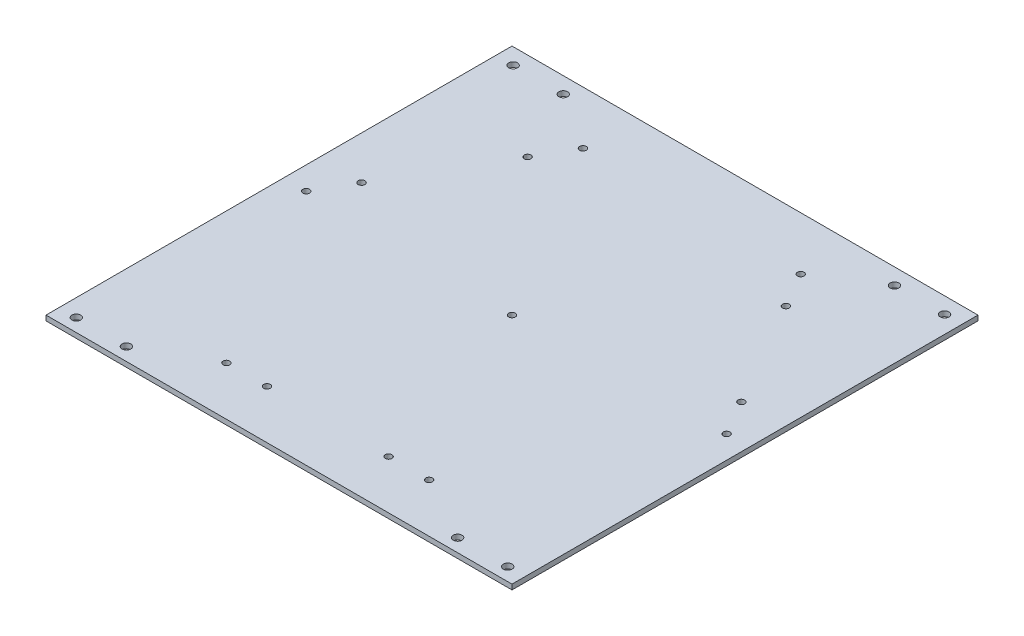
SolidWorks part; units mm, degrees
material "CA"
ref_plane "Front Plane" through (0, 0, 0) normal (0, 0, 1) x (1, 0, 0)
ref_plane "Top Plane" through (0, 0, 0) normal (0, 1, 0) x (1, 0, 0)
ref_plane "Right Plane" through (0, 0, 0) normal (1, 0, 0) x (0, 0, -1)
sketch "Sketch1" plane through (0, 0, 0) normal (0, 1, 0) x (1, 0, 0)
  line L1 (146.05, 146.05) -> (-146.05, 146.05)
  line L2 (-146.05, 146.05) -> (-146.05, -146.05)
  line L3 (-146.05, -146.05) -> (146.05, -146.05)
  line L4 (146.05, -146.05) -> (146.05, 146.05)
  circle A0 centre (0, 0) radius 146.05 construction
  dimension "D1" = 292.1
extrude "Boss-Extrude1" add sketch "Sketch1" along normal blind 3.175
sketch "Sketch2" plane through (0, 3.175, 0) normal (0, 1, 0) x (1, 0, 0)
  line L1 (133.35, 0) -> (66.675, 115.4845) construction
  line L2 (66.675, 115.4845) -> (-66.675, 115.4845) construction
  line L3 (-66.675, 115.4845) -> (-133.35, 0) construction
  line L4 (-133.35, 0) -> (-66.675, -115.4845) construction
  line L5 (-66.675, -115.4845) -> (66.675, -115.4845) construction
  line L6 (66.675, -115.4845) -> (133.35, 0) construction
  circle A0 centre (0, 0) radius 133.35 construction
  dimension "D1" = 266.7
hole_wizard "M5x0.8 Tapped Hole2" positions "Sketch7" profile "Sketch8" tap size "M5x0.8" standard "ANSI Metric" end condition through all
sketch "Sketch7" plane through (0, 3.175, 0) normal (0, 1, 0) x (1, 0, 0)
  line L0 (-66.675, -115.4845) -> (66.675, -115.4845) construction
  line L1 (-63.5, -115.4845) -> (-38.1, -115.4845) construction
  line L2 (-38.1, -115.4845) -> (38.1, -115.4845) construction
  line L3 (38.1, -115.4845) -> (63.5, -115.4845) construction
  line L5 (-146.05, -146.05) -> (146.05, -146.05) construction
  line L6 (-68.2625, 112.7349) -> (-80.9625, 90.7378) construction
  line L7 (-80.9625, 90.7378) -> (-119.0625, 24.7467) construction
  line L8 (-119.0625, 24.7467) -> (-131.7625, 2.7496) construction
  line L9 (131.7625, 2.7496) -> (119.0625, 24.7467) construction
  line L10 (119.0625, 24.7467) -> (80.9625, 90.7378) construction
  line L11 (80.9625, 90.7378) -> (68.2625, 112.7349) construction
  point P0 (-63.5, -115.4845)
  point P4 (-38.1, -115.4845)
  point P6 (38.1, -115.4845)
  point P8 (63.5, -115.4845)
  point P25 (0, -115.4845)
  point P26 (0, -146.05)
  point P28 (-50.8, -115.4845)
  point P29 (50.8, -115.4845)
  point P34 (-68.2625, 112.7349)
  point P35 (-80.9625, 90.7378)
  point P36 (-119.0625, 24.7467)
  point P37 (-131.7625, 2.7496)
  point P42 (131.7625, 2.7496)
  point P43 (119.0625, 24.7467)
  point P44 (80.9625, 90.7378)
  point P45 (68.2625, 112.7349)
  point P50 (0, 0)
  dimension "D1" = 25.4
  dimension "D2" = 101.6
  dimension "D3" = 3
sketch "Sketch8" plane through (-63.5, 3.175, 115.4845) normal (1, 0, 0) x (0, 0, 1)
  line L0 (0, 0) -> (0, 3.175)
  line L1 (0, 3.175) -> (2.1, 3.175)
  line L2 (2.1, 3.175) -> (2.1, 0)
  line L5 (2.1, 0) -> (0, 0)
  line L11 (0, -6.35) -> (0, 107.95) construction
  dimension "Thru Tap Drill Dia." = 4.2
  dimension "Thru Tap Drill Depth" = 3.175
cosmetic thread "Hole Thread16" parameters "D2"=5
cosmetic thread "Hole Thread17" parameters "D2"=5
cosmetic thread "Hole Thread18" parameters "D2"=5
cosmetic thread "Hole Thread19" parameters "D2"=5
cosmetic thread "Hole Thread20" parameters "D2"=5
cosmetic thread "Hole Thread21" parameters "D2"=5
cosmetic thread "Hole Thread22" parameters "D2"=5
cosmetic thread "Hole Thread23" parameters "D2"=5
cosmetic thread "Hole Thread24" parameters "D2"=5
cosmetic thread "Hole Thread25" parameters "D2"=5
cosmetic thread "Hole Thread26" parameters "D2"=5
cosmetic thread "Hole Thread27" parameters "D2"=5
cosmetic thread "Hole Thread28" parameters "D2"=5
hole_wizard "M5 Clearance Hole1" positions "Sketch9" profile "Sketch10" hole size "M5" standard "ANSI Metric"
sketch "Sketch9" plane through (0, 3.175, 0) normal (0, 1, 0) x (1, 0, 0)
  line L0 (-135.2162, 135.9269) -> (-135.2162, -137.892) construction
  line L2 (135.2162, -137.892) -> (135.2162, 135.9269) construction
  line L4 (-135.2162, 135.9269) -> (-103.802, 135.9269) construction
  line L5 (-103.802, 135.9269) -> (103.802, 135.9269) construction
  line L6 (103.802, 135.9269) -> (135.2162, 135.9269) construction
  line L8 (-135.2162, -137.892) -> (-103.802, -137.892) construction
  line L9 (-103.802, -137.892) -> (103.802, -137.892) construction
  line L10 (103.802, -137.892) -> (135.2162, -137.892) construction
  point P0 (-135.2162, -137.892)
  point P2 (-103.802, -137.892)
  point P4 (103.802, -137.892)
  point P6 (135.2162, -137.892)
  point P8 (103.802, 135.9269)
  point P10 (135.2162, 135.9269)
  point P12 (-135.2162, 135.9269)
  point P14 (-103.802, 135.9269)
  point P42 (0, -137.892)
sketch "Sketch10" plane through (-135.2162, 3.175, 137.892) normal (1, 0, 0) x (0, 0, 1)
  line L0 (0, 0) -> (0, 27.0524)
  line L1 (0, 27.0524) -> (2.75, 25.4)
  line L2 (2.75, 25.4) -> (2.75, 0)
  line L5 (2.75, 0) -> (0, 0)
  line L10 (0, 27.0524) -> (-2.75, 25.4) construction
  line L11 (0, -6.35) -> (0, 107.95) construction
  dimension "Hole Dia." = 5.5
  dimension "Hole Depth" = 25.4
  dimension "Drill Angle" = 118
